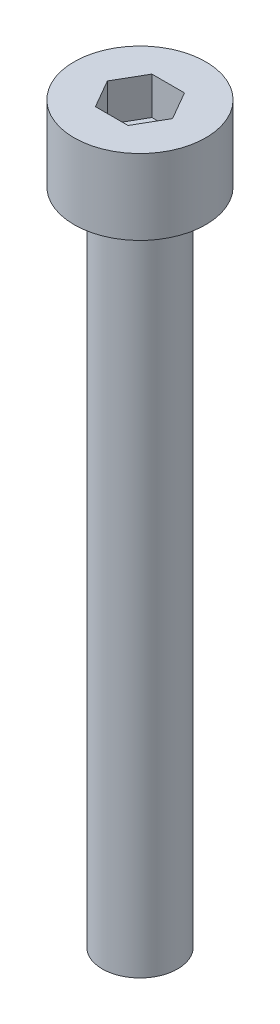
SolidWorks part; units mm, degrees
material "普通碳钢"
ref_plane "前视基准面" through (0, 0, 0) normal (0, 0, 1) x (1, 0, 0)
ref_plane "上视基准面" through (0, 0, 0) normal (0, 1, 0) x (1, 0, 0)
ref_plane "右视基准面" through (0, 0, 0) normal (1, 0, 0) x (0, 0, -1)
sketch "草图1" plane through (0, 0, 0) normal (0, 1, 0) x (1, 0, 0)
  circle A0 centre (0, 0) radius 2
  circle A1 centre (0, 0) radius 3.5
  dimension "公称直径" = 4
  dimension "外径" = 7
extrude "头部高" add sketch "草图1" along normal blind 4 contours A0 | A1 A0 region at (0, 0, 0) region at (-3.401, 0, 0)
extrude "公称长度" add sketch "草图1<3>" against normal blind 35 contours A0 region at (0, 0, 0)
sketch "草图1<3>" plane through (0, 0, 0) normal (0, 1, 0) x (1, 0, 0) same geometry as "草图1"
sketch "草图2" plane through (0, 4, 0) normal (0, 1, 0) x (1, 0, 0)
  line L1 (1.7321, 0) -> (0.866, 1.5)
  line L2 (0.866, 1.5) -> (-0.866, 1.5)
  line L3 (-0.866, 1.5) -> (-1.7321, 0)
  line L4 (-1.7321, 0) -> (-0.866, -1.5)
  line L5 (-0.866, -1.5) -> (0.866, -1.5)
  line L6 (0.866, -1.5) -> (1.7321, 0)
  circle A0 centre (0, 0) radius 1.5 construction
  dimension "D1" = 3
extrude "切除-拉伸1" cut sketch "草图2" against normal blind 2
